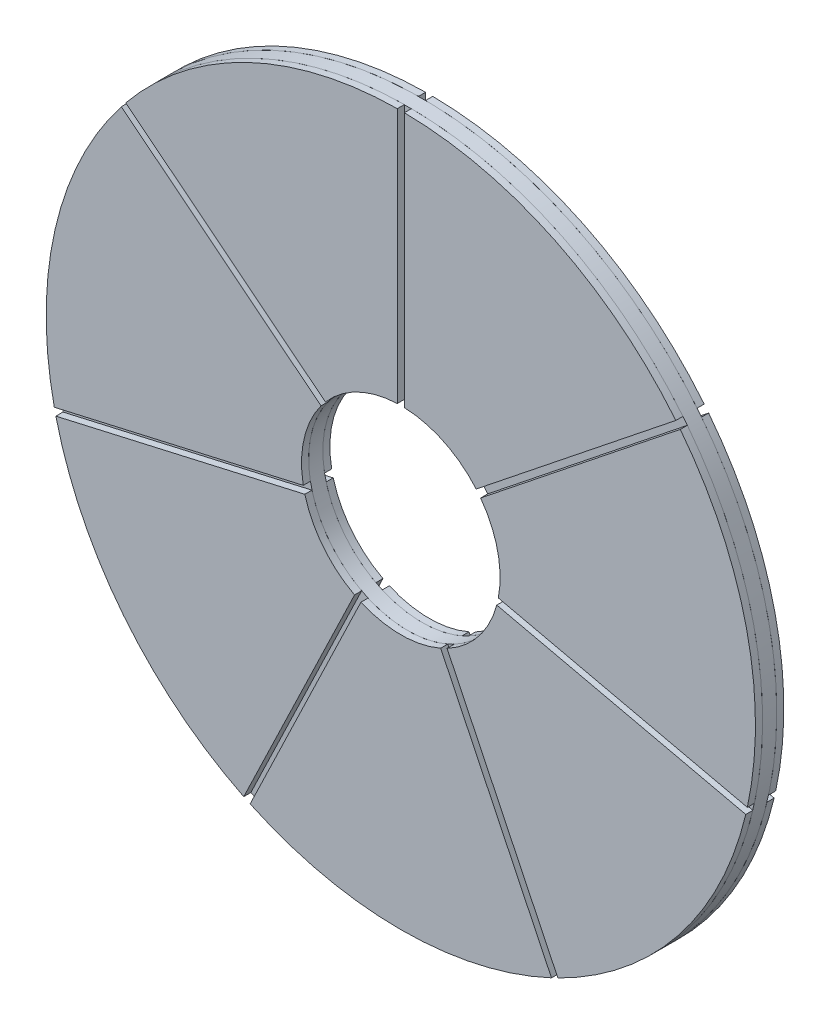
SolidWorks part; units mm, degrees
ref_plane "Front Plane" through (0, 0, 0) normal (0, 0, 1) x (1, 0, 0)
ref_plane "Top Plane" through (0, 0, 0) normal (0, 1, 0) x (1, 0, 0)
ref_plane "Right Plane" through (0, 0, 0) normal (1, 0, 0) x (0, 0, -1)
sketch "Sketch1" plane through (0, 0, 0) normal (0, 0, 1) x (1, 0, 0)
  circle A0 centre (0, 0) radius 12.5
  dimension "D1" = 25
extrude "Boss-Extrude1" add sketch "Sketch1" along normal blind 0.25 and the other way blind 0.25 contours A0
sketch "Sketch2" plane through (0, 0, 0.25) normal (0, 0, 1) x (1, 0, 0)
  line L0 (-0.0779, 0.0977) -> (0.0779, -0.0977)
  line L1 (-0.125, 0) -> (0.125, 0)
  line L2 (-0.125, 0) -> (-0.125, 19.4123)
  line L3 (-0.125, 19.4123) -> (0.125, 19.4123)
  line L4 (0.125, 0) -> (0.125, 19.4123)
  line L5 (-0.0779, 0.0977) -> (15.0992, 12.2011)
  line L6 (15.0992, 12.2011) -> (15.255, 12.0056)
  line L7 (0.0779, -0.0977) -> (15.255, 12.0056)
  line L8 (0.0278, 0.1219) -> (-0.0278, -0.1219)
  line L9 (0.0278, 0.1219) -> (18.9534, -4.1978)
  line L10 (18.9534, -4.1978) -> (18.8977, -4.4415)
  line L11 (-0.0278, -0.1219) -> (18.8977, -4.4415)
  line L12 (0.1126, 0.0542) -> (-0.1126, -0.0542)
  line L13 (0.1126, 0.0542) -> (8.5353, -17.4356)
  line L14 (8.5353, -17.4356) -> (8.31, -17.5441)
  line L15 (-0.1126, -0.0542) -> (8.31, -17.5441)
  line L16 (0.1126, -0.0542) -> (-0.1126, 0.0542)
  line L17 (0.1126, -0.0542) -> (-8.31, -17.5441)
  line L18 (-8.31, -17.5441) -> (-8.5353, -17.4356)
  line L19 (-0.1126, 0.0542) -> (-8.5353, -17.4356)
  line L20 (0.0278, -0.1219) -> (-0.0278, 0.1219)
  line L21 (0.0278, -0.1219) -> (-18.8977, -4.4415)
  line L22 (-18.8977, -4.4415) -> (-18.9534, -4.1978)
  line L23 (-0.0278, 0.1219) -> (-18.9534, -4.1978)
  line L24 (-0.0779, -0.0977) -> (0.0779, 0.0977)
  line L25 (-0.0779, -0.0977) -> (-15.255, 12.0056)
  line L26 (-15.255, 12.0056) -> (-15.0992, 12.2011)
  line L27 (0.0779, 0.0977) -> (-15.0992, 12.2011)
  circle A0 centre (0, 0) radius 19
  point P7 (0, 0)
  point P15 (0, 0)
  point P19 (0, 0)
  point P21 (0, 0)
  point P26 (0, 0)
  point P31 (0, 0)
  point P36 (0, 0)
  point P41 (0, 0)
  point P42 (0, 0)
  circle M1 centre (0, 0) radius 12.5
  dimension "D1" = 7
  dimension "D2" = 38
extrude "Boss-Extrude2" add sketch "Sketch2" along normal blind 0.25 separate body contours L4 L5 M1 | L27 L2 M1 | L23 L25 M1 | L19 L21 M1 | L15 L17 M1 | L11 L13 M1 | L7 L9 M1 region at (3.5424, 7.3558, 0.25) region at (-3.5424, 7.3558, 0.25) region at (-7.9597, 1.8167, 0.25) region at (7.9597, 1.8167, 0.25) region at (6.3831, -5.0904, 0.25) region at (0, -8.1643, 0.25) region at (-6.3831, -5.0904, 0.25)
mirror "Mirror5" about plane through (0, 0, 0) normal (0, 0, 1) of bodies 125 124 164 122 120 123 163 104 103 102 141
sketch "Sketch3" plane through (0, 0, 0) normal (0, 0, 1) x (1, 0, 0)
  circle A0 centre (0, 0) radius 3.5
  dimension "D1" = 7
extrude "Cut-Extrude2" cut sketch "Sketch3" against normal blind 8.35 and the other way blind 10 contours A0
